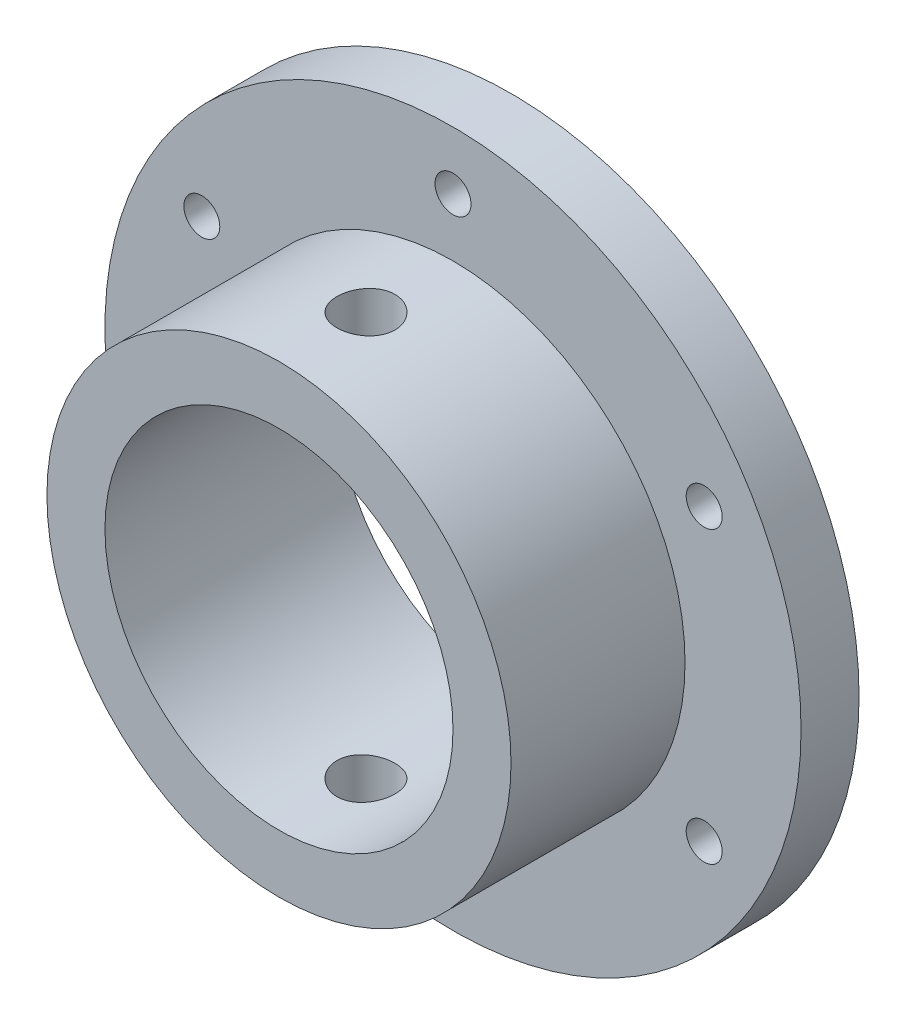
SolidWorks part; units mm, degrees
ref_plane "Front Plane" through (0, 0, 0) normal (0, 0, 1) x (1, 0, 0)
ref_plane "Top Plane" through (0, 0, 0) normal (0, 1, 0) x (1, 0, 0)
ref_plane "Right Plane" through (0, 0, 0) normal (1, 0, 0) x (0, 0, -1)
sketch "Sketch1" plane through (0, 0, 0) normal (0, 0, 1) x (1, 0, 0)
  circle A0 centre (0, 0) radius 30
  point P0 (0, 0)
  dimension "D1" = 60
extrude "Boss-Extrude1" add sketch "Sketch1" along normal blind 5
sketch "Sketch2" plane through (0, 0, 5) normal (0, 0, 1) x (1, 0, 0)
  circle A0 centre (0, 0) radius 20
  circle A1 centre (0, 0) radius 15
  dimension "D1" = 40
extrude "Boss-Extrude2" add sketch "Sketch2" along normal blind 15
sketch "Sketch3" plane through (0, 0, 5) normal (0, 0, 1) x (1, 0, 0)
  circle A0 centre (0, 0) radius 15
  dimension "D1" = 30
extrude "Cut-Extrude1" cut sketch "Sketch3" against normal blind 20
sketch "Sketch5" plane through (0, 0, 0) normal (0, 1, 0) x (1, 0, 0)
  line L0 (-20, -5) -> (20, -5) construction
  circle A0 centre (0, -12.5) radius 2.5
  dimension "D1" = 7.5
extrude "Cut-Extrude3" cut sketch "Sketch5" against normal through all both and the other way through all
sketch "Sketch6" plane through (0, 0, 5) normal (0, 0, 1) x (1, 0, 0)
  circle A0 centre (0, 0) radius 25 construction
  circle A1 centre (0, 25) radius 1.55
  circle A2 centre (21.6506, 12.5) radius 1.55
  circle A3 centre (21.6506, -12.5) radius 1.55
  circle A4 centre (0, -25) radius 1.55
  circle A5 centre (-21.6506, -12.5) radius 1.55
  circle A6 centre (-21.6506, 12.5) radius 1.55
  point P17 (0, 0)
  dimension "D1" = 50
  dimension "D2" = 6
  dimension "D3" = 3.1
extrude "Cut-Extrude4" cut sketch "Sketch6" against normal blind 10
